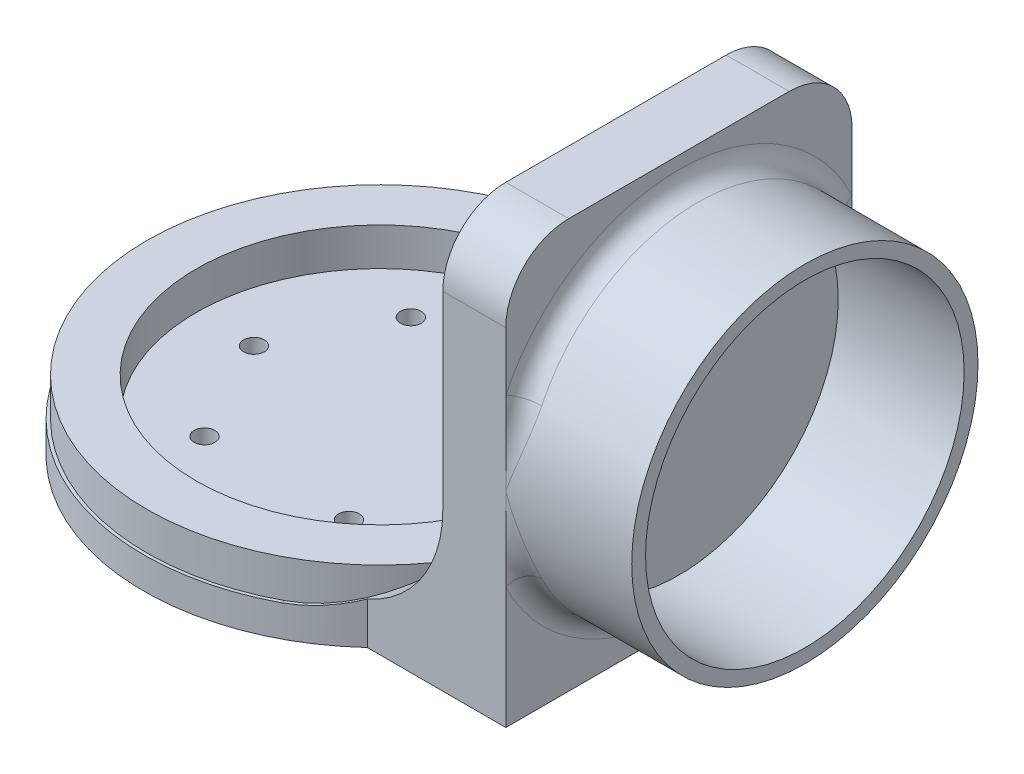
SolidWorks part; units mm, degrees
ref_plane "Front Plane" through (0, 0, 0) normal (0, 0, 1) x (1, 0, 0)
ref_plane "Top Plane" through (0, 0, 0) normal (0, 1, 0) x (1, 0, 0)
ref_plane "Right Plane" through (0, 0, 0) normal (1, 0, 0) x (0, 0, -1)
sketch "Sketch1" plane through (0, 0, 0) normal (0, 1, 0) x (1, 0, 0)
  circle A0 centre (0, 0) radius 37.5
  dimension "D1" = 75
extrude "Boss-Extrude1" add sketch "Sketch1" along normal blind 5
ref_plane "Plane1" through (37.5, 0, 0) normal (1, 0, 0) x (0, 0, -1)
sketch "Sketch2" plane through (37.5, 0, 0) normal (1, 0, 0) x (0, 0, -1)
  line L0 (0, 0) -> (0, 5) construction
  line L1 (37.5, 5) -> (-37.5, 5) construction
  line L3 (27.5, 0) -> (-27.5, 0)
  line L4 (27.5, 0) -> (27.5, 5)
  line L9 (27.5, 5) -> (-27.5, 5)
  line L10 (-27.5, 0) -> (-27.5, 5)
  line L11 (0, 5) -> (0, 0) construction
  line L12 (27.5, 2.5) -> (-27.5, 2.5) construction
  point P4 (0, 2.5)
extrude "Boss-Extrude2" add sketch "Sketch2" along normal blind 10 and the other way up to next
sketch "Sketch3" plane through (0, 5, 0) normal (0, 1, 0) x (1, 0, 0)
  line L0 (0, 0) -> (20, 0) construction
  line L1 (0, 0) -> (11.4715, 16.383) construction
  line L2 (0, 0) -> (11.4715, -16.383) construction
  line L3 (0, 0) -> (0, 15.5364) construction
  circle A0 centre (20, 0) radius 1.65
  circle A1 centre (11.4715, 16.383) radius 1.65
  circle A2 centre (11.4715, -16.383) radius 1.65
  circle A3 centre (-11.4715, -16.383) radius 1.65
  circle A4 centre (-20, 0) radius 1.65
  circle A5 centre (-11.4715, 16.383) radius 1.65
  dimension "D3" = 3.3
  dimension "D1" = 55
  dimension "D2" = 55
extrude "Cut-Extrude1" cut sketch "Sketch3" against normal blind 40
sketch "Sketch4" plane through (0, 5, 0) normal (0, 1, 0) x (1, 0, 0)
  line L7 (37.5, -2.75) -> (37.5, 2.75) construction
  line L8 (47.5, -27.5) -> (37.5, -27.5)
  line L9 (47.5, -27.5) -> (47.5, 27.5)
  line L10 (47.5, 27.5) -> (37.5, 27.5)
  line L11 (37.5, -27.5) -> (37.5, 27.5)
  line L12 (47.5, 27.5) -> (25.4951, 27.5) construction
extrude "Boss-Extrude3" add sketch "Sketch4" along normal blind 60
sketch "Sketch5" plane through (0, 5, 0) normal (0, 1, 0) x (1, 0, 0)
  circle A0 centre (0, 0) radius 37
  circle A1 centre (0, 0) radius 29.1778
extrude "Boss-Extrude4" add sketch "Sketch5" along normal blind 6
fillet "Fillet3" radius 20 1 edges at (37.5, 5, 0)
sketch "Sketch6" plane through (47.5, 0, 0) normal (1, 0, 0) x (0, 0, -1)
  line L0 (0, 0) -> (0, 65) construction
  line L1 (-27.5, 65) -> (27.5, 65) construction
  circle A0 centre (0, 32.5) radius 25.3
  circle A1 centre (0, 32.5) radius 27.5
  dimension "D1" = 50.6
extrude "Boss-Extrude5" add sketch "Sketch6" along normal blind 20
fillet "Fillet4" radius 3 2 edges at (47.5, 5, 0) (47.5, 60, 0)
fillet "Fillet5" radius 10 2 edges at (42.5, 65, 27.5) (42.5, 65, -27.5)
sketch "Sketch7" plane through (37.5, 0, 0) normal (-1, 0, 0) x (0, 0, 1)
  line L0 (0, 65) -> (0, 11) construction
  line L1 (-17.5, 65) -> (17.5, 65) construction
  line L2 (37, 11) -> (-37, 11) construction
  circle A0 centre (0, 38) radius 5
  dimension "D1" = 10
extrude "Cut-Extrude2" cut sketch "Sketch7" against normal blind 10
